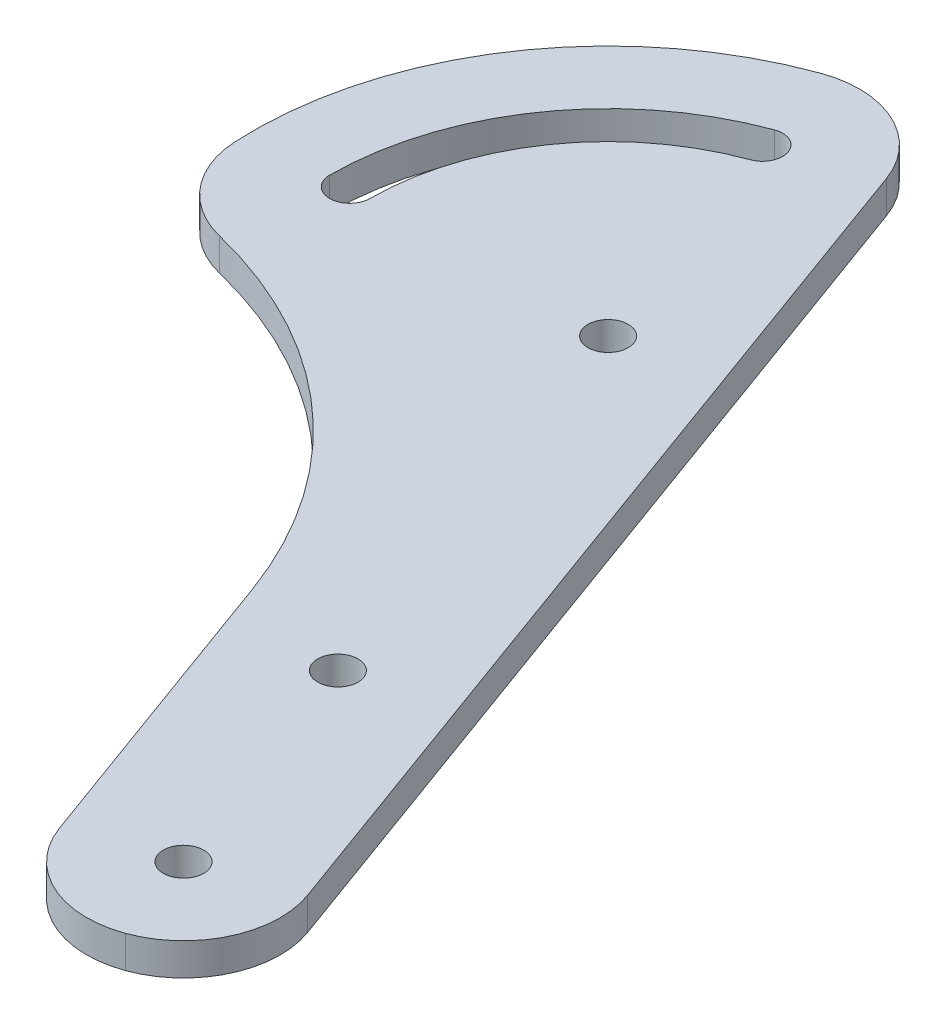
SolidWorks part; units mm, degrees
material "7075-T6, Plate (SS)"
ref_plane "Front Plane" through (0, 0, 0) normal (0, 0, 1) x (1, 0, 0)
ref_plane "Top Plane" through (0, 0, 0) normal (0, 1, 0) x (1, 0, 0)
ref_plane "Right Plane" through (0, 0, 0) normal (1, 0, 0) x (0, 0, -1)
sketch "Sketch1" plane through (0, 0, 0) normal (0, 1, 0) x (1, 0, 0)
  line L8 (101.6, 19.05) -> (152.4, 19.05) construction
  line L9 (0, 0) -> (228.6, 0) construction
  line L11 (0, 0) -> (0, 38.1) construction
  line L12 (0, 38.1) -> (228.6, 38.1) construction
  line L13 (228.6, 0) -> (228.6, 38.1) construction
  line L14 (160.5608, -59.0701) -> (188.7946, -136.6417)
  line L15 (188.7946, -136.6417) -> (224.5968, -123.6107)
  line L16 (224.5968, -123.6107) -> (196.3631, -46.0391)
  line L17 (182.8056, -64.4887) -> (200.1802, -112.2251) construction
  line L18 (196.3631, -46.0391) -> (160.5608, -59.0701) construction
  line L19 (196.3631, -46.0391) -> (147.3167, 88.7148)
  arc A1 (101.6, 19.05) -> (135.0254, 66.7864) centre (152.4, 19.05) cw construction
  arc A2 (147.3167, 88.7148) -> (85.1979, 0) centre (152.4, 19.05) ccw
  arc A3 (85.1979, 0) -> (160.5608, -59.0701) centre (75.4484, -90.0484) cw
  arc A4 (105.5687, 19.05) -> (136.3828, 63.057) centre (152.4, 19.05) cw
  arc A5 (97.6313, 19.05) -> (133.668, 70.5158) centre (152.4, 19.05) cw
  arc A6 (105.5687, 19.05) -> (97.6313, 19.05) centre (101.6, 19.05) cw
  arc A7 (136.3828, 63.057) -> (133.668, 70.5158) centre (135.0254, 66.7864) ccw
  point P6 (0, 19.05)
  point P15 (206.6957, -130.1262)
  dimension "D4" = 38.1
  dimension "D9" = 76.2
  dimension "D11" = 19.05
  dimension "D12" = 3.9688
  dimension "D1" = 38.1
  dimension "D2" = 228.6
  dimension "D3" = 50.8
  dimension "D5" = 50.8
  dimension "D6" = 19.05
  dimension "D7" = 12.7
  dimension "D8" = 70
  dimension "D10" = 76.2
  dimension "D13" = 3.9687
sketch "Sketch5" plane through (0, 0, 0) normal (0, 1, 0) x (1, 0, 0)
  line L0 (0, 0) -> (0, 38.1)
  line L1 (0, 38.1) -> (177.8, 38.1)
  line L2 (177.8, 38.1) -> (211.0179, -85.8708)
  line L4 (12.7, 19.05) -> (165.1, 19.05) construction
  line L5 (172.895, -17.1978) -> (192.617, -90.8013) construction
  line L6 (126.6259, -52.7013) -> (192.617, -90.8013) construction
  line L7 (0, 0) -> (188.0089, 0) construction
  line L8 (188.0089, 0) -> (151.7779, -9.7081) construction
  line L9 (0, 0) -> (182.9851, -107.2369)
  arc A0 (172.895, -17.1978) -> (126.6259, -52.7013) centre (192.617, -90.8013) ccw construction
  arc A1 (211.0179, -85.8708) -> (182.9851, -107.2369) centre (192.617, -90.8013) cw
  arc A2 (171.8678, -13.3642) -> (123.1888, -50.7169) centre (192.617, -90.8013) ccw
  arc A3 (173.9222, -21.0313) -> (130.0629, -54.6857) centre (192.617, -90.8013) ccw
  arc A4 (171.8678, -13.3642) -> (173.9222, -21.0313) centre (172.895, -17.1978) cw
  arc A5 (123.1888, -50.7169) -> (130.0629, -54.6857) centre (126.6259, -52.7013) ccw
  point P12 (0, 19.05)
  dimension "D8" = 45
  dimension "D10" = 12.7
  dimension "D2" = 19.05
  dimension "D1" = 38.1
  dimension "D3" = 152.4
  dimension "D4" = 76.2
  dimension "D5" = 3.9688
  dimension "D6" = 12.7
  dimension "D7" = 60
  dimension "D9" = 12.7
  dimension "D11" = 3.9688
extrude "Boss-Extrude2" [suppressed] add sketch "Sketch5" along normal blind 6.35 separate body
hole_wizard "5/16 (0.3125) Diameter Hole1" [suppressed] positions "Sketch6" profile "Sketch7" hole size "5/16" standard "ANSI Inch"
sketch "Sketch6" [suppressed] plane through (0, 6.35, 0) normal (0, 1, 0) x (1, 0, 0)
  point P0 (12.7, 19.05)
  point P3 (165.1, 19.05)
  point P6 (192.617, -90.8013)
sketch "Sketch7" plane through (12.7, 6.35, -19.05) normal (1, 0, 0) x (0, 0, 1)
  line L0 (0, 0) -> (0, 6.35)
  line L1 (0, 6.35) -> (3.9687, 6.35)
  line L2 (3.9687, 6.35) -> (3.9687, 0)
  line L5 (3.9687, 0) -> (0, 0)
  line L11 (0, -6.35) -> (0, 107.95) construction
  dimension "Thru Hole Dia." = 7.9375
  dimension "Thru Hole Depth" = 6.35
fillet "Fillet1" [suppressed] radius 19.05
extrude "Boss-Extrude3" add sketch "Sketch1" along normal blind 6.35
hole_wizard "5/16 (0.3125) Diameter Hole2" positions "Sketch8" profile "Sketch9" hole size "5/16" standard "ANSI Inch" end condition through all
sketch "Sketch8" plane through (0, 6.35, 0) normal (0, 1, 0) x (1, 0, 0)
  point P0 (152.4, 19.05)
  point P3 (182.8056, -64.4887)
  point P6 (200.1802, -112.2251)
sketch "Sketch9" plane through (152.4, 6.35, -19.05) normal (1, 0, 0) x (0, 0, 1)
  line L0 (0, 0) -> (0, 6.35)
  line L1 (0, 6.35) -> (3.9687, 6.35)
  line L2 (3.9687, 6.35) -> (3.9687, 0)
  line L5 (3.9687, 0) -> (0, 0)
  line L11 (0, -6.35) -> (0, 107.95) construction
  dimension "Thru Hole Dia." = 7.9375
  dimension "Thru Hole Depth" = 6.35
fillet "Fillet2" radius 19.05 4 edges at (147.3167, 3.175, -88.7148) (224.5968, 3.175, 123.6107) (188.7946, 3.175, 136.6417) (85.1979, 3.175, 0)
